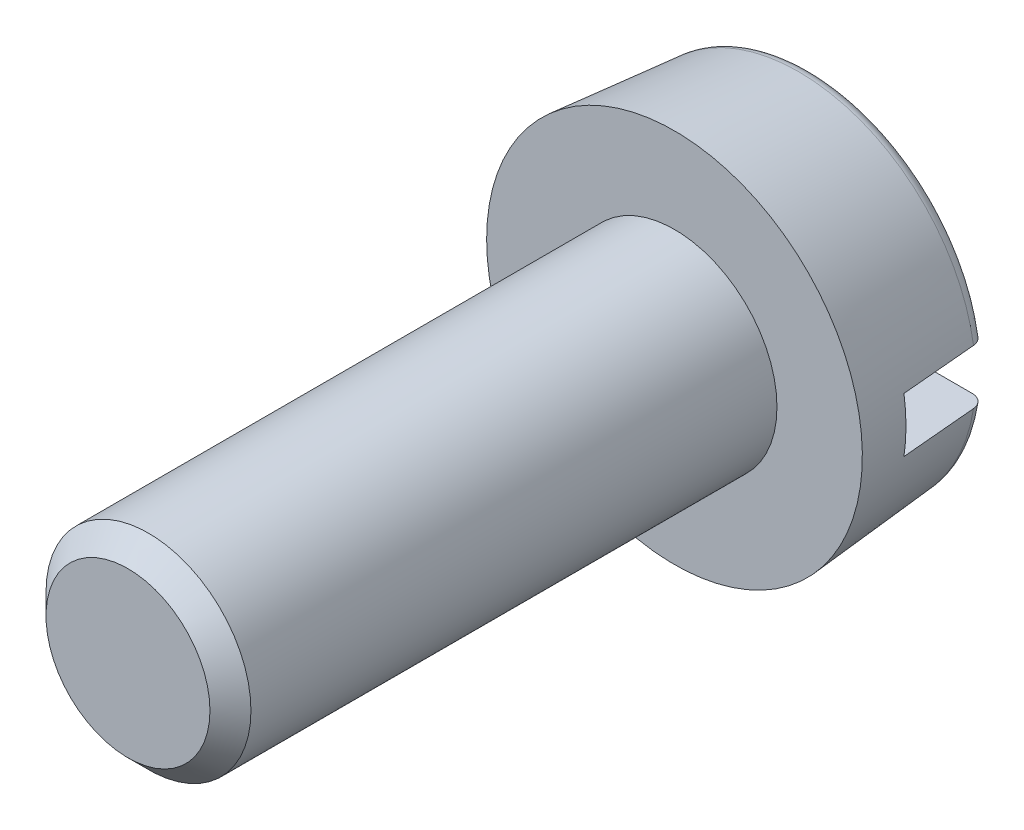
SolidWorks part; units mm, degrees
note: '?' marks a value the reader was unsure of.
ref_plane "Plan1" through (0, 0, 0) normal (0, 0, 1) x (1, 0, 0)
ref_plane "Plan2" through (0, 0, 0) normal (0, 1, 0) x (1, 0, 0)
ref_plane "Plan3" through (0, 0, 0) normal (1, 0, 0) x (0, 0, -1)
ref_axis "Z Axis" through (0, 0, -50) along (0, 0, 1)?
sketch "Esquisse1" plane through (0, 0, 0) normal (0, 1, 0) x (1, 0, 0)
  line L0 (0, 0) -> (0, 2) construction
  line L1 (0, 0) -> (2.75, 0)
  line L2 (0, 0) -> (0, 2)
  line L3 (0, 2) -> (2.3918, 2)
  line L5 (2.75, 0) -> (2.591, 1.8174)
  arc A0 (2.3918, 2) -> (2.591, 1.8174) centre (2.3918, 1.8) cw
  dimension "D3" = 0.2
  dimension "D1" = 2.75
  dimension "D2" = 2
  dimension "D4" = 5
revolve "Base-Révolution" add sketch "Esquisse1" angle 360 about L0
sketch "Esquisse2" plane through (0, 0, -2) normal (0, 0, 1) x (1, 0, 0)
  line L1 (-2.75, 0.4) -> (2.75, 0.4)
  line L2 (-2.75, 0.4) -> (-2.75, -0.4)
  line L3 (-2.75, -0.4) -> (2.75, -0.4)
  line L4 (2.75, 0.4) -> (2.75, -0.4)
  circle A0 centre (0, 0) radius 2.75 construction
  dimension "D1" = 0.4
extrude "Enlev. mat.-Extru.1" cut sketch "Esquisse2" along normal blind 1.3
sketch "Esquisse3" plane through (0, 0, 0) normal (0, 1, 0) x (1, 0, 0)
  line L1 (0, 0) -> (0, -8) construction
  line L2 (0, 0) -> (1.5, 0)
  line L3 (0, 0) -> (0, -8)
  line L4 (0, -8) -> (1.5, -8)
  line L6 (1.5, 0) -> (1.5, -8)
  dimension "D1" = 8
  dimension "D2" = 1.5
revolve "Boss.-Révol.1" add sketch "Esquisse3"
cosmetic thread "Représentation de filetage1"
chamfer "Chanfrein1" distance 0.3 angle 45
